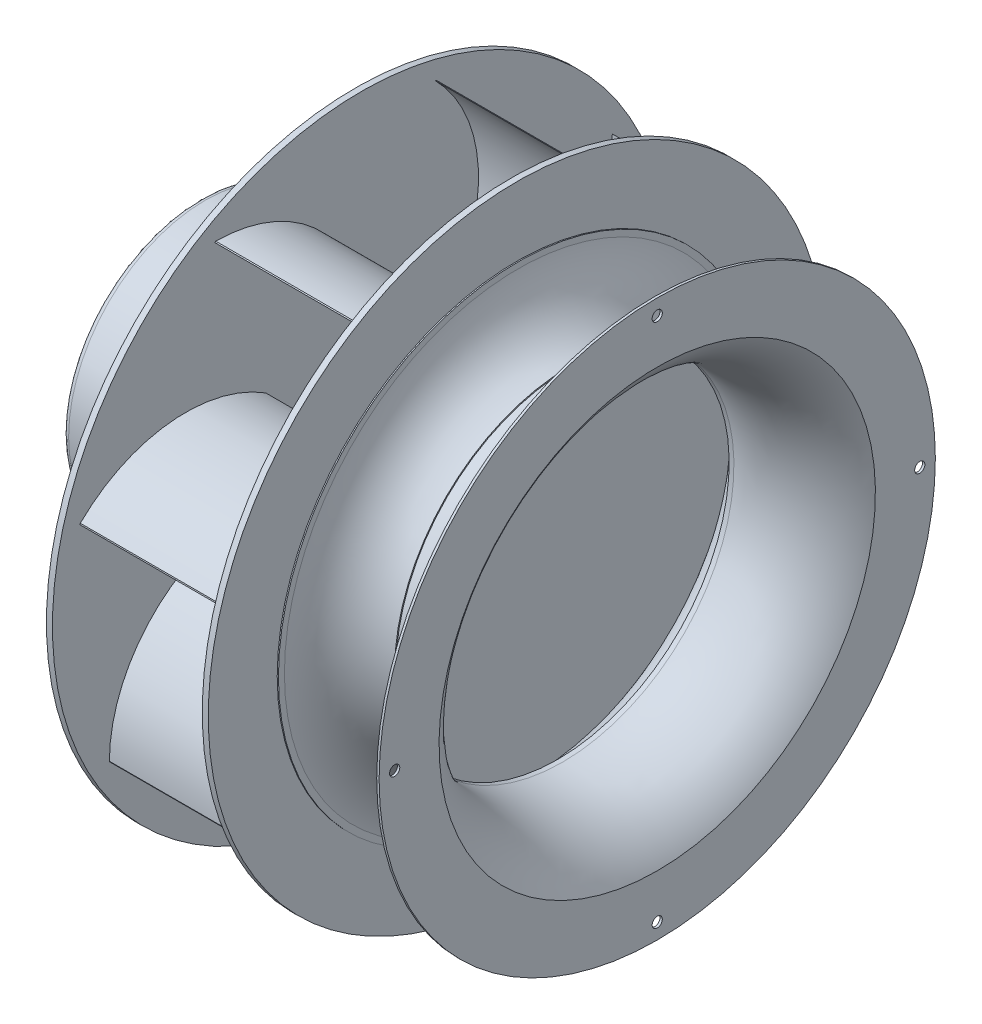
SolidWorks part; units mm, degrees
ref_plane "Front Plane" through (0, 0, 0) normal (0, 0, 1) x (1, 0, 0)
ref_plane "Top Plane" through (0, 0, 0) normal (0, 1, 0) x (1, 0, 0)
ref_plane "Right Plane" through (0, 0, 0) normal (1, 0, 0) x (0, 0, -1)
sketch "Sketch1" plane through (0, 0, 0) normal (0, 0, 1) x (1, 0, 0)
  line L0 (0, 0) -> (831.9083, 0) construction
  line L1 (0, 0) -> (0, 109)
  line L2 (5, 114) -> (70, 114)
  line L3 (70, 114) -> (70, 138)
  line L4 (70, 138) -> (90, 138)
  line L5 (90, 138) -> (90, 98)
  line L6 (90, 98) -> (95, 98)
  line L7 (95, 98) -> (95, 133)
  line L8 (95, 133) -> (105, 133)
  line L9 (105, 133) -> (105, 98)
  line L10 (105, 98) -> (130, 98)
  line L11 (130, 98) -> (130, 0)
  line L12 (130, 0) -> (0, 0)
  arc A0 (5, 114) -> (0, 109) centre (5, 109) ccw
  point P16 (0, 114)
  dimension "D10" = 5
  dimension "D1" = 114
  dimension "D2" = 24
  dimension "D3" = 70
  dimension "D4" = 40
  dimension "D5" = 35
  dimension "D6" = 5
  dimension "D7" = 20
  dimension "D8" = 10
  dimension "D9" = 60
revolve "Revolve1" add sketch "Sketch1" angle 360 about L0
sketch "Sketch2" plane through (130, 0, 0) normal (1, 0, 0) x (0, 0, -1)
  circle A0 centre (0, 0) radius 257.5
  dimension "D1" = 515
extrude "Extrude1" add sketch "Sketch2" along normal blind 5
sketch "Sketch9" plane through (130, 0, 0) normal (-1, 0, 0) x (0, 0, 1)
  circle A0 centre (0, 0) radius 252.5
  circle A1 centre (0, 0) radius 100
  circle A2 centre (0, 0) radius 257.5 construction
  dimension "D1" = 5
  dimension "D2" = 200
extrude "Extrude7" cut sketch "Sketch9" against normal blind 3
ref_plane "Plane1" through (260, 0, 0) normal (1, 0, 0) x (0, 0, -1)
sketch "Sketch3" plane through (260, 0, 0) normal (1, 0, 0) x (0, 0, -1)
  circle A0 centre (0, 0) radius 257.5
  dimension "D1" = 515
extrude "Extrude2" add sketch "Sketch3" along normal blind 5 separate body
sketch "Sketch4" plane through (135, 0, 0) normal (1, 0, 0) x (0, 0, -1)
  line L0 (0, 0) -> (0, 242.5) construction
  line L1 (0, 0) -> (128.75, 223.0015) construction
  line L2 (0, 112.5) -> (0.866, 112) construction
  line L3 (121.25, 210.0112) -> (122.116, 209.5112) construction
  line L4 (-121.25, 210.0112) -> (-122.116, 209.5112)
  line L5 (0, 112.5) -> (-0.866, 112)
  circle A0 centre (0, 0) radius 242.5 construction
  circle A1 centre (0, 0) radius 257.5 construction
  circle A2 centre (0, 0) radius 112.5 construction
  arc A3 (0, 112.5) -> (121.25, 210.0112) centre (121.9404, 85.0131) cw construction
  arc A4 (0.866, 112) -> (122.116, 209.5112) centre (122.8065, 84.5131) cw construction
  arc A5 (0, 112.5) -> (-121.25, 210.0112) centre (-121.9404, 85.0131) ccw
  arc A6 (-0.866, 112) -> (-122.116, 209.5112) centre (-122.8065, 84.5131) ccw
  dimension "D1" = 15
  dimension "D2" = 225
  dimension "D6" = 125
  dimension "D7" = 125
  dimension "D3" = 30
  dimension "D4" = 60
  dimension "D5" = 1
extrude "Extrude3" add sketch "Sketch4" along normal up to surface (130 mm away) up to face at (265, 0, -257.5)
ref_axis "Axis1" through (253.5503, 0, 0) along (-1, 0, 0)
pattern_circular "CirPattern1" count 8 over 360 about axis through (253.5503, 0, 0) along (-1, 0, 0) of "Extrude3"
sketch "Sketch5" plane through (0, 0, 0) normal (0, 0, 1) x (1, 0, 0)
  line L0 (0, 0) -> (527.2916, 0) construction
  line L1 (253.5503, 0) -> (75.411, 0) construction
  line L2 (265, 200) -> (266, 200)
  line L3 (266, 200) -> (266, 195)
  line L4 (265, 200) -> (265, 195)
  line L5 (309, 146) -> (309, 145)
  line L6 (70, 138) -> (70, -138) construction
  line L7 (265, -257.5) -> (265, 257.5) construction
  arc A0 (266, 195) -> (309, 146) centre (325.3621, 203.7259) ccw
  arc A1 (265, 195) -> (309, 145) centre (324.4681, 202.9719) ccw
  dimension "D7" = 60
  dimension "D8" = 60
  dimension "D1" = 145
  dimension "D2" = 1
  dimension "D3" = 1
  dimension "D4" = 5
  dimension "D5" = 200
  dimension "D6" = 239
revolve "Revolve2" add sketch "Sketch5" angle 360 about L0
ref_plane "Plane3" through (382, 0, 0) normal (1, 0, 0) x (0, 0, -1)
sketch "Sketch6" plane through (0, 0, 0) normal (0, 0, 1) x (1, 0, 0)
  line L0 (382, 232) -> (380, 232)
  line L1 (382, -251.35) -> (382, 251.35) construction
  line L2 (380, 232) -> (380, 182)
  line L3 (0, 0) -> (615.1417, 0) construction
  line L4 (0, 114) -> (0, -114) construction
  line L5 (253.5503, 0) -> (75.411, 0) construction
  line L6 (382, 232) -> (382, 182)
  line L7 (299, 145) -> (303, 145)
  line L8 (299, 145) -> (299, 143)
  line L9 (299, 143) -> (303, 143)
  arc A0 (303, 145) -> (380, 182) centre (312.2033, 224.4689) ccw
  arc A1 (303, 143) -> (382, 182) centre (312.9389, 222.3802) ccw
  dimension "D7" = 80
  dimension "D8" = 80
  dimension "D1" = 232
  dimension "D2" = 2
  dimension "D3" = 182
  dimension "D4" = 83
  dimension "D5" = 145
  dimension "D6" = 4
revolve "Revolve3" add sketch "Sketch6" angle 360 about L3
sketch "Sketch7" plane through (382, 0, 0) normal (1, 0, 0) x (0, 0, -1)
  line L0 (0, 0) -> (0, 219) construction
  circle A0 centre (0, 0) radius 219 construction
  circle A1 centre (0, 219) radius 4.25
  dimension "D1" = 438
  dimension "D2" = 8.5
extrude "Extrude5" cut sketch "Sketch7" against normal blind 5
pattern_circular "CirPattern2" count 4 over 360 about axis through (253.5503, 0, 0) along (-1, 0, 0) of "Extrude5"
sketch "Sketch8" plane through (0, 0, 0) normal (1, 0, 0) x (0, 0, -1)
  line L0 (0, 0) -> (0, 126) construction
  circle A0 centre (0, 0) radius 126 construction
  circle A1 centre (0, 126) radius 5
  dimension "D1" = 252
  dimension "D2" = 10
extrude "Extrude6" cut sketch "Sketch8" along normal up to surface (90 mm away) up to face at (90, 0, 138)
pattern_circular "CirPattern3" count 8 over 360 about axis through (253.5503, 0, 0) along (-1, 0, 0) of "Extrude6"
